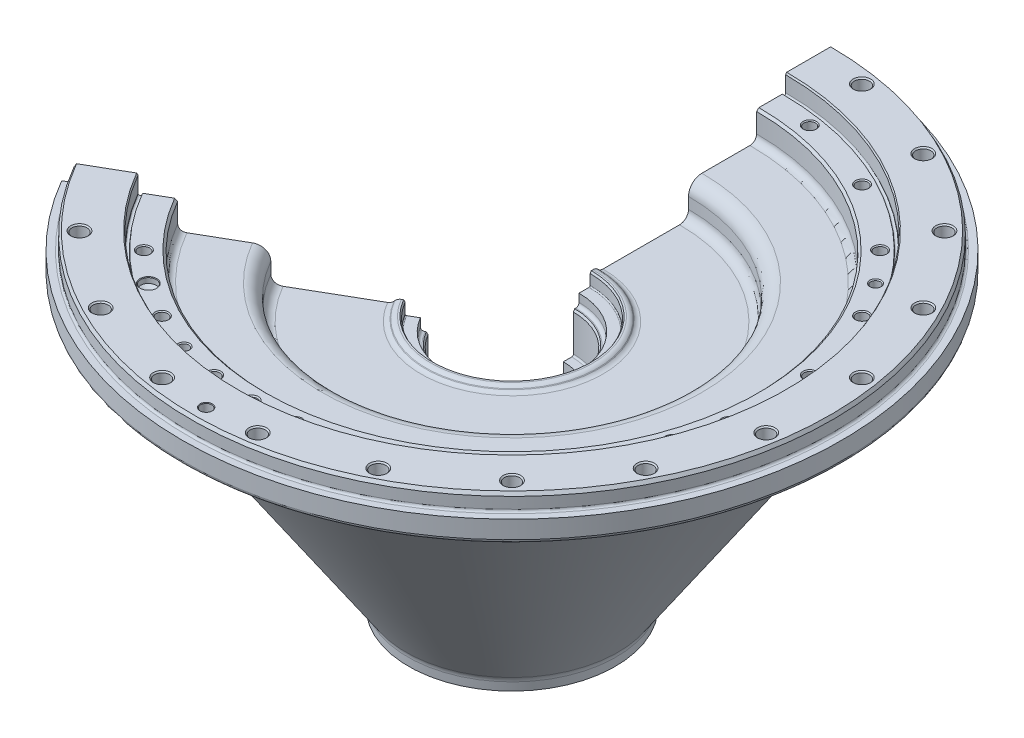
SolidWorks part; units mm, degrees
ref_plane "Front Plane" through (0, 0, 0) normal (0, 0, 1) x (1, 0, 0)
ref_plane "Top Plane" through (0, 0, 0) normal (0, 1, 0) x (1, 0, 0)
ref_plane "Right Plane" through (0, 0, 0) normal (1, 0, 0) x (0, 0, -1)
sketch "Sketch1" plane through (0, 0, 0) normal (0, 0, 1) x (1, 0, 0)
  line L0 (57, -133) -> (0, -133)
  line L1 (0, -133) -> (0, -258)
  line L2 (0, -258) -> (53.5, -258)
  line L3 (55, -259.5) -> (55, -308)
  line L4 (55, -308) -> (62.5, -308)
  line L5 (62.5, -308) -> (62.5, -320)
  line L6 (62.5, -320) -> (64, -322.5981)
  line L7 (64, -322.5981) -> (64, -333)
  line L8 (64, -333) -> (66, -335)
  line L9 (66, -335) -> (66, -340)
  line L10 (66, -340) -> (73.05, -340)
  line L11 (73.05, -340) -> (73.05, -337.5)
  line L12 (73.05, -337.5) -> (72.617, -336.75)
  line L13 (73.05, -336) -> (92.5, -336)
  line L14 (92.5, -336) -> (93.5732, -325.7893)
  line L15 (93.5732, -325.7893) -> (238.3378, -111.2416)
  line L16 (249, -107.1204) -> (249, -78.456)
  line L17 (249, -78.456) -> (295, -78.456)
  line L18 (295, -78.456) -> (295, -59.5)
  line L19 (295, -59.5) -> (287, -59.5)
  line L20 (287, -59.5) -> (287, -47.5)
  line L21 (287, -47.5) -> (285.2679, -44.5)
  line L22 (285.2679, -44.5) -> (245, -44.5)
  line L23 (245, -44.5) -> (245, -60)
  line L24 (242, -60) -> (242, -59.5)
  line L25 (242, -59.5) -> (158, -59.5)
  line L26 (158, -59.5) -> (158, -114.85)
  line L27 (158, -114.85) -> (70, -114.85)
  line L28 (70, -114.85) -> (70, -122.85)
  line L29 (70, -122.85) -> (60, -122.85)
  line L30 (60, -122.85) -> (60, -130)
  line L31 (0, -44.5) -> (0, -340) construction
  arc A0 (53.5, -258) -> (55, -259.5) centre (53.5, -259.5) cw
  arc A1 (72.617, -336.75) -> (73.05, -336) centre (73.05, -336.5) cw
  arc A2 (238.3378, -111.2416) -> (249, -107.1204) centre (246.6273, -116.8349) cw
  arc A3 (245, -60) -> (242, -60) centre (243.5, -60) cw
  arc A4 (60, -130) -> (57, -133) centre (57, -130) cw
revolve "Revolve1" add sketch "Sketch1" angle 360 about L31 reverse direction yes
sketch "Sketch2" plane through (0, -133, 0) normal (0, 1, 0) x (-1, 0, 0)
  circle A0 centre (0, 0) radius 56.1547
extrude "Cut-Extrude1" cut sketch "Sketch2" against normal blind 2 draft 30
sketch "Sketch3" plane through (0, -135, 0) normal (0, 1, 0) x (-1, 0, 0)
  circle A0 centre (0, 0) radius 55
extrude "Cut-Extrude2" cut sketch "Sketch3" against normal blind 34
ref_plane "Plane1" through (0, -243, 0) normal (0, -1, 0) x (1, 0, 0)
sketch "Sketch4" plane through (0, -243, 0) normal (0, -1, 0) x (1, 0, 0)
  circle A0 centre (0, 0) radius 60
extrude "Cut-Extrude3" cut sketch "Sketch4" against normal blind 59
sketch "Sketch5" plane through (0, -184, 0) normal (0, -1, 0) x (1, 0, 0)
  circle A0 centre (0, 0) radius 46
extrude "Cut-Extrude4" cut sketch "Sketch5" against normal through all
sketch "Sketch6" plane through (0, -258, 0) normal (0, -1, 0) x (1, 0, 0)
  circle A0 centre (0, 0) radius 38.5
extrude "Cut-Extrude5" cut sketch "Sketch6" against normal blind 4
sketch "Sketch7" plane through (0, -243, 0) normal (0, 1, 0) x (-1, 0, 0)
  circle A0 centre (0, 0) radius 28.5
extrude "Cut-Extrude6" cut sketch "Sketch7" against normal through all
sketch "Sketch8" plane through (0, 0, 0) normal (0, 0, 1) x (1, 0, 0)
  line L0 (161, -117.85) -> (161, -117.5103)
  line L1 (160.7238, -117.85) -> (161, -117.85)
  line L2 (0, -117.5103) -> (0, -117.85) construction
  arc A0 (161, -117.5103) -> (160.7238, -117.85) centre (150, -108.85) cw
revolve "Cut-Revolve1" cut sketch "Sketch8" angle 360 about L2 reverse direction yes
sketch "Sketch9" plane through (0, 0, 0) normal (0, 0, 1) x (1, 0, 0)
  line L0 (219, -59.5) -> (158, -59.5)
  line L1 (158, -59.5) -> (158, -84.85)
  line L2 (158, -84.85) -> (219, -84.85)
  line L3 (219, -84.85) -> (219, -59.5)
  line L4 (0, -59.5) -> (0, -84.85) construction
revolve "Cut-Revolve2" cut sketch "Sketch9" angle 360 about L4 reverse direction yes
sketch "Sketch10" plane through (0, 0, 0) normal (0, 0, 1) x (1, 0, 0)
  line L0 (75, -110.85) -> (70, -110.85)
  line L1 (70, -110.85) -> (70, -114.85)
  line L2 (70, -114.85) -> (79, -114.85)
  line L3 (79, -114.85) -> (75, -110.85)
  line L4 (0, -110.85) -> (0, -114.85) construction
revolve "Revolve2" add sketch "Sketch10" angle 360 about L4 reverse direction yes
hole_wizard "M8 Clearance Hole1" positions "Sketch12" profile "Sketch11" hole size "M8" standard "ANSI Metric"
sketch "Sketch12" plane through (0, -114.85, 0) normal (0, 1, 0) x (1, 0, 0)
  point P0 (-79.4536, -32.9108)
sketch "Sketch11" plane through (-79.4536, -114.85, 32.9108) normal (1, 0, 0) x (0, 0, 1)
  line L0 (0, 0) -> (0, 150.15)
  line L1 (0, 150.15) -> (4.2164, 147.6165)
  line L2 (4.2164, 147.6165) -> (4.2164, 0)
  line L5 (4.2164, 0) -> (0, 0)
  line L10 (0, 150.15) -> (-4.2164, 147.6165) construction
  line L11 (0, -6.35) -> (0, 107.95) construction
  dimension "Hole Dia." = 8.4328
  dimension "Hole Depth" = 147.6165
  dimension "Drill Angle" = 118
hole_wizard "Ø8.5 (8.5) Diameter Hole1" positions "Sketch14" profile "Sketch13" hole size "Ø8.5" standard "ANSI Metric"
sketch "Sketch14" plane through (0, -336, 0) normal (0, -1, 0) x (-1, 0, 0)
  point P0 (-41.275, -71.4904)
  point P1 (41.275, -71.4904)
  point P2 (58.3717, 58.3717)
  point P3 (-58.3717, 58.3717)
sketch "Sketch13" plane through (41.275, -336, 71.4904) normal (1, 0, 0) x (0, 0, -1)
  line L0 (0, 0) -> (0, 37.5537)
  line L1 (0, 37.5537) -> (4.25, 35)
  line L2 (4.25, 35) -> (4.25, 0)
  line L5 (4.25, 0) -> (0, 0)
  line L10 (0, 37.5537) -> (-4.25, 35) construction
  line L11 (0, -6.35) -> (0, 107.95) construction
  dimension "Hole Dia." = 8.5
  dimension "Hole Depth" = 35
  dimension "Drill Angle" = 118
hole_wizard "Ø13.5 (13.5) Diameter Hole1" positions "Sketch16" profile "Sketch15" hole size "Ø13.5" standard "ANSI Metric"
sketch "Sketch16" plane through (0, -44.5, 0) normal (0, 1, 0) x (1, 0, 0)
  point P0 (270.3797, 42.8239)
  point P1 (243.913, -124.2799)
  point P2 (243.913, 124.2799)
  point P3 (193.5705, -193.5705)
  point P4 (193.5705, 193.5705)
  point P5 (124.2799, -243.913)
  point P6 (124.2799, 243.913)
  point P7 (42.8239, -270.3797)
  point P8 (42.8239, 270.3797)
  point P9 (-42.8239, -270.3797)
  point P10 (-42.8239, 270.3797)
  point P11 (-124.2799, -243.913)
  point P12 (-124.2799, 243.913)
  point P13 (-193.5705, -193.5705)
  point P14 (-193.5705, 193.5705)
  point P15 (-243.913, -124.2799)
  point P16 (-243.913, 124.2799)
  point P17 (-270.3797, -42.8239)
  point P18 (-270.3797, 42.8239)
sketch "Sketch15" plane through (270.3797, -44.5, -42.8239) normal (1, 0, 0) x (0, 0, 1)
  line L0 (0, 0) -> (0, 295.5)
  line L1 (0, 295.5) -> (6.75, 295.5)
  line L2 (6.75, 295.5) -> (6.75, 0)
  line L5 (6.75, 0) -> (0, 0)
  line L11 (0, -6.35) -> (0, 107.95) construction
  dimension "Thru Hole Dia." = 13.5
  dimension "Thru Hole Depth" = 295.5
hole_wizard "Ø13.5 (13.5) Diameter Hole2" positions "Sketch18" profile "Sketch17" hole size "Ø13.5" standard "ANSI Metric"
sketch "Sketch18" plane through (0, -78.456, 0) normal (0, -1, 0) x (-1, 0, 0)
  point P0 (-270.3797, -42.8239)
sketch "Sketch17" plane through (270.3797, -78.456, 42.8239) normal (1, 0, 0) x (0, 0, -1)
  line L0 (0, 0) -> (0, 33.956)
  line L1 (0, 33.956) -> (6.75, 33.956)
  line L2 (6.75, 33.956) -> (6.75, 0)
  line L5 (6.75, 0) -> (0, 0)
  line L11 (0, -6.35) -> (0, 107.95) construction
  dimension "Thru Hole Dia." = 13.5
  dimension "Thru Hole Depth" = 33.956
hole_wizard "Ø10.0 (10) Diameter Hole1" positions "Sketch20" profile "Sketch19" hole size "Ø10.0" standard "ANSI Metric"
sketch "Sketch20" plane through (0, -44.5, 0) normal (0, 1, 0) x (1, 0, 0)
  point P0 (0, -273.75)
sketch "Sketch19" plane through (0, -44.5, 273.75) normal (1, 0, 0) x (0, 0, 1)
  line L0 (0, 0) -> (0, 295.5)
  line L1 (0, 295.5) -> (5, 295.5)
  line L2 (5, 295.5) -> (5, 0)
  line L5 (5, 0) -> (0, 0)
  line L11 (0, -6.35) -> (0, 107.95) construction
  dimension "Thru Hole Dia." = 10
  dimension "Thru Hole Depth" = 295.5
hole_wizard "Hole1" positions "Sketch22" profile "Sketch21" legacy
sketch "Sketch22" plane through (0, -59.5, 0) normal (0, 1, 0) x (1, 0, 0)
  point P0 (230.1314, -36.4492)
  point P1 (230.1314, 36.4492)
  point P2 (207.6045, -105.7798)
  point P3 (207.6045, 105.7798)
  point P4 (164.7559, -164.7559)
  point P5 (164.7559, 164.7559)
  point P6 (105.7798, -207.6045)
  point P7 (105.7798, 207.6045)
  point P8 (36.4492, -230.1314)
  point P9 (36.4492, 230.1314)
  point P10 (-36.4492, -230.1314)
  point P11 (-36.4492, 230.1314)
  point P12 (-105.7798, -207.6045)
  point P13 (-105.7798, 207.6045)
  point P14 (-164.7559, -164.7559)
  point P15 (-164.7559, 164.7559)
  point P16 (-207.6045, -105.7798)
  point P17 (-207.6045, 105.7798)
  point P18 (-230.1314, -36.4492)
  point P19 (-230.1314, 36.4492)
sketch "Sketch21" plane through (230.1314, -59.5, 36.4492) normal (1, 0, 0) x (0, 0, 1)
  line L0 (0, 0) -> (0, 41.0944)
  line L1 (0, 41.0944) -> (5.15, 38)
  line L2 (5.15, 38) -> (5.15, 0)
  line L4 (5.15, 0) -> (0, 0)
  line L6 (0, 41.0944) -> (-5.15, 38) construction
  line L7 (0, -4.2442) -> (0, 117.3081) construction
  dimension "Diameter" = 10.3
  dimension "Depth" = 38
  dimension "Drill Angle" = 118
hole_wizard "Ø10.0 (10) Diameter Hole2" positions "Sketch24" profile "Sketch23" hole size "Ø10.0" standard "ANSI Metric"
sketch "Sketch24" plane through (0, -59.5, 0) normal (0, 1, 0) x (1, 0, 0)
  point P0 (0, -233)
sketch "Sketch23" plane through (0, -59.5, 233) normal (1, 0, 0) x (0, 0, 1)
  line L0 (0, 0) -> (0, 16.0043)
  line L1 (0, 16.0043) -> (5, 13)
  line L2 (5, 13) -> (5, 0)
  line L5 (5, 0) -> (0, 0)
  line L10 (0, 16.0043) -> (-5, 13) construction
  line L11 (0, -6.35) -> (0, 107.95) construction
  dimension "Hole Dia." = 10
  dimension "Hole Depth" = 13
  dimension "Drill Angle" = 118
hole_wizard "Ø14.0 (14) Diameter Hole1" positions "Sketch26" profile "Sketch25" hole size "Ø14.0" standard "ANSI Metric"
sketch "Sketch26" plane through (0, -59.5, 0) normal (0, 1, 0) x (1, 0, 0)
  point P0 (220.3058, -75.8574)
  point P1 (-54.3928, 226.5622)
  point P2 (-136.954, -188.501)
sketch "Sketch25" plane through (220.3058, -59.5, 75.8574) normal (1, 0, 0) x (0, 0, 1)
  line L0 (0, 0) -> (0, 9.206)
  line L1 (0, 9.206) -> (7, 5)
  line L2 (7, 5) -> (7, 0)
  line L5 (7, 0) -> (0, 0)
  line L10 (0, 9.206) -> (-7, 5) construction
  line L11 (0, -6.35) -> (0, 107.95) construction
  dimension "Hole Dia." = 14
  dimension "Hole Depth" = 5
  dimension "Drill Angle" = 118
hole_wizard "Ø8.5 (8.5) Diameter Hole2" positions "Sketch28" profile "Sketch27" hole size "Ø8.5" standard "ANSI Metric"
sketch "Sketch28" plane through (0, -59.5, 0) normal (0, 1, 0) x (1, 0, 0)
  point P0 (188.501, -136.954)
  point P1 (188.501, 136.954)
  point P2 (-72.001, -221.5962)
  point P3 (-72.001, 221.5962)
  point P4 (-233, 0)
sketch "Sketch27" plane through (188.501, -59.5, 136.954) normal (1, 0, 0) x (0, 0, 1)
  line L0 (0, 0) -> (0, 32.5537)
  line L1 (0, 32.5537) -> (4.25, 30)
  line L2 (4.25, 30) -> (4.25, 0)
  line L5 (4.25, 0) -> (0, 0)
  line L10 (0, 32.5537) -> (-4.25, 30) construction
  line L11 (0, -6.35) -> (0, 107.95) construction
  dimension "Hole Dia." = 8.5
  dimension "Hole Depth" = 30
  dimension "Drill Angle" = 118
ref_plane "Plane2" through (-136.8129, 0, 56.6698) normal (-0.9239, 0, 0.3827) x (0.3827, 0, 0.9239)
hole_wizard "CBORE for M8 Hex Head Bolt1" positions "Sketch30" profile "Sketch29" counterbore size "M8" standard "ANSI Metric"
sketch "Sketch30" plane through (-136.8129, 0, 56.6698) normal (-0.9239, 0, 0.3827) x (0.3827, 0, 0.9239)
  point P0 (0, -255)
sketch "Sketch29" plane through (-136.8129, -255, 56.6698) normal (0, 1, 0) x (0.3827, 0, 0.9239)
  line L0 (0, 0) -> (0, 119.8811)
  line L1 (0, 119.8811) -> (4.2164, 119.8811)
  line L2 (4.2164, 119.8811) -> (4.2164, 48.8688)
  line L3 (4.2164, 48.8688) -> (10, 48.8688)
  line L4 (10, 48.8688) -> (10, 0)
  line L5 (10, 0) -> (0, 0)
  line L10 (0, 119.8811) -> (-4.2164, 119.8811) construction
  line L11 (0, -6.35) -> (0, 107.95) construction
  dimension "Hole Dia." = 8.4328
  dimension "Hole Depth" = 119.8811
  dimension "C'Bore Dia." = 20
  dimension "C'Bore Depth" = 48.8688
  dimension "Drill Angle" = 180
ref_plane "Plane3" through (-204.2607, -127.6465, 84.6076) normal (-0.8001, -0.5, 0.3314) x (0.281, 0.1756, 0.9435)
hole_wizard "CBORE for M8 Hex Head Bolt2" positions "Sketch32" profile "Sketch31" counterbore size "M8" standard "ANSI Metric"
sketch "Sketch32" plane through (-204.2607, -127.6465, 84.6076) normal (-0.8001, -0.5, 0.3314) x (0.281, 0.1756, 0.9435)
  point P0 (-16.884, -81.5231)
sketch "Sketch31" plane through (-165.8028, -199.7459, 68.6778) normal (-0.1474, 0.6994, 0.6994) x (0.5815, -0.5107, 0.6333)
  line L0 (0, 0) -> (0, 140.379)
  line L1 (0, 140.379) -> (4.2164, 140.379)
  line L2 (4.2164, 140.379) -> (4.2164, 83.4917)
  line L3 (4.2164, 83.4917) -> (10, 83.4917)
  line L4 (10, 83.4917) -> (10, 0)
  line L5 (10, 0) -> (0, 0)
  line L10 (0, 140.379) -> (-4.2164, 140.379) construction
  line L11 (0, -6.35) -> (0, 107.95) construction
  dimension "Hole Dia." = 8.4328
  dimension "Hole Depth" = 140.379
  dimension "C'Bore Dia." = 20
  dimension "C'Bore Depth" = 83.4917
  dimension "Drill Angle" = 180
hole_wizard "Ø12.0 (12) Diameter Hole1" positions "Sketch34" profile "Sketch33" hole size "Ø12.0" standard "ANSI Metric"
sketch "Sketch34" plane through (0, -243, 0) normal (0, 1, 0) x (1, 0, 0)
  point P0 (54, 0)
sketch "Sketch33" plane through (54, -243, 0) normal (1, 0, 0) x (0, 0, 1)
  line L0 (0, 0) -> (0, 97)
  line L1 (0, 97) -> (6, 97)
  line L2 (6, 97) -> (6, 0)
  line L5 (6, 0) -> (0, 0)
  line L11 (0, -6.35) -> (0, 107.95) construction
  dimension "Thru Hole Dia." = 12
  dimension "Thru Hole Depth" = 97
chamfer "Chamfer1" distance 1.1 angle 45 40 edges at (49.5739, -78.456, -270.3797) (277.1297, -78.456, -42.8239) (-237.163, -78.456, -124.2799) (200.3205, -78.456, -193.5705) (-117.5299, -78.456, -243.913) (250.663, -78.456, -124.2799) (131.0299, -78.456, -243.913) (-36.0739, -78.456, -270.3797) (-186.8205, -78.456, -193.5705) (-263.6297, -78.456, -42.8239) (270.3797, -44.5, 36.0739) (270.3797, -78.456, 36.0739) (270.3797, -44.5, -36.0739) (250.663, -78.456, 124.2799) (243.913, -44.5, 131.0299) (200.3205, -78.456, 193.5705) (243.913, -44.5, -117.5299) (131.0299, -78.456, 243.913) (193.5705, -44.5, 200.3205) (49.5739, -78.456, 270.3797) (193.5705, -44.5, -186.8205) (-36.0739, -78.456, 270.3797) (124.2799, -44.5, 250.663) (-117.5299, -78.456, 243.913) (124.2799, -44.5, -237.163) (-186.8205, -78.456, 193.5705) (42.8239, -44.5, 277.1297) (-237.163, -78.456, 124.2799) (42.8239, -44.5, -263.6297) (-263.6297, -78.456, 42.8239) (-42.8239, -44.5, 277.1297) (-42.8239, -44.5, -263.6297) (-124.2799, -44.5, 250.663) (-270.3797, -44.5, -36.0739) (-243.913, -44.5, -117.5299) (-270.3797, -44.5, 49.5739) (-193.5705, -44.5, -186.8205) (-243.913, -44.5, 131.0299) (-124.2799, -44.5, -237.163) (-193.5705, -44.5, 200.3205) first distance on face at (5, -78.456, 273.75) first distance on face at (0, -44.5, 278.75)
chamfer "Chamfer2" distance 0.85 angle 45 29 edges at (105.7798, -59.5, -202.4545) (36.4492, -59.5, 235.2814) (164.7559, -59.5, -159.6059) (36.4492, -59.5, -224.9814) (-36.4492, -59.5, 235.2814) (-36.4492, -59.5, -224.9814) (-41.275, -336, 67.2404) (-105.7798, -59.5, 212.7545) (188.501, -59.5, 141.204) (-105.7798, -59.5, -202.4545) (-164.7559, -59.5, 169.9059) (-164.7559, -59.5, -159.6059) (-207.6045, -59.5, 110.9298) (-207.6045, -59.5, -100.6298) (-230.1314, -59.5, 41.5992) (-230.1314, -59.5, -31.2992) (105.7798, -59.5, 212.7545) (58.3717, -336, -62.6217) (188.501, -59.5, -132.704) (41.275, -336, 67.2404) (-58.3717, -336, -62.6217) (-233, -59.5, 4.25) (207.6045, -59.5, -100.6298) (-72.001, -59.5, 225.8462) (-72.001, -59.5, -217.3462) (207.6045, -59.5, 110.9298) (164.7559, -59.5, 169.9059) (230.1314, -59.5, 41.5992) (230.1314, -59.5, -31.2992) first distance on face at (188.501, -59.5, 141.204) first distance on face at (41.275, -336, 67.2404)
chamfer "Chamfer3" distance 1 angle 45 1 edges at (0, -59.5, 238) first distance on face at (99.7798, -59.5, -207.6045)
chamfer "Chamfer4" distance 1.7321 angle 60 1 edges at (-55, -308, 0) first distance on face at (2.5, -308, 0)
chamfer "Chamfer5" distance 0.5 angle 45 5 edges at (220.3058, -59.5, 82.8574) (5, -78.456, 273.75) (-136.954, -59.5, 195.501) (0, -44.5, 278.75) (-54.3928, -59.5, -219.5622)
chamfer "Chamfer6" distance 1 angle 60 1 edges at (0, -110.85, -70) first distance on face at (0, -110.85, -70)
chamfer "Chamfer7" distance 0.433 angle 60 1 edges at (73.05, -340, 0) first distance on face at (73.05, -340, 0)
chamfer "Chamfer8" distance 0.866 angle 60 1 edges at (245, -44.5, 0) first distance on face at (-5.5, -44.5, 273.75)
chamfer "Chamfer9" distance 2 angle 45 1 edges at (0, -59.5, -219) first distance on face at (0, -59.5, -219)
fillet "Fillet1" radius 1 1 edges at (70, -122.85, 0) tangent propagation no
fillet "Fillet2" radius 1.5 2 edges at (55, -169, 0) (62.5, -308, 0) tangent propagation no
fillet "Fillet3" radius 2 1 edges at (287, -59.5, 0) tangent propagation no
fillet "Fillet4" radius 3 2 edges at (295, -78.456, 0) (249, -107.1204, 0) tangent propagation no
fillet "Fillet5" radius 6 3 edges at (0, -84.85, -219) (0, -110.85, -75) (-79, -114.85, 0) tangent propagation no
fillet "Fillet6" radius 8 1 edges at (158, -114.85, 0) tangent propagation no
fillet "Fillet7" radius 10 4 edges at (0, -243, 60) (0, -184, 60) (249, -78.456, 0) (93.5732, -325.7893, 0) tangent propagation no
fillet "Fillet8" radius 12 1 edges at (0, -84.85, -158) tangent propagation no
sketch "Sketch35" plane through (0, -44.5, 0) normal (0, 1, 0) x (1, 0, 0)
  line L0 (0, 0) -> (-466.8601, -270.163)
  line L1 (-466.8601, -270.163) -> (-310.247, 316.6655)
  line L2 (-310.247, 316.6655) -> (27.8978, 402.138)
  line L3 (27.8978, 402.138) -> (0, 285.2679)
  line L4 (0, 285.2679) -> (0, 0)
  circle A0 centre (0, 0) radius 285.2679 construction
extrude "Cut-Extrude7" cut sketch "Sketch35" against normal through all
